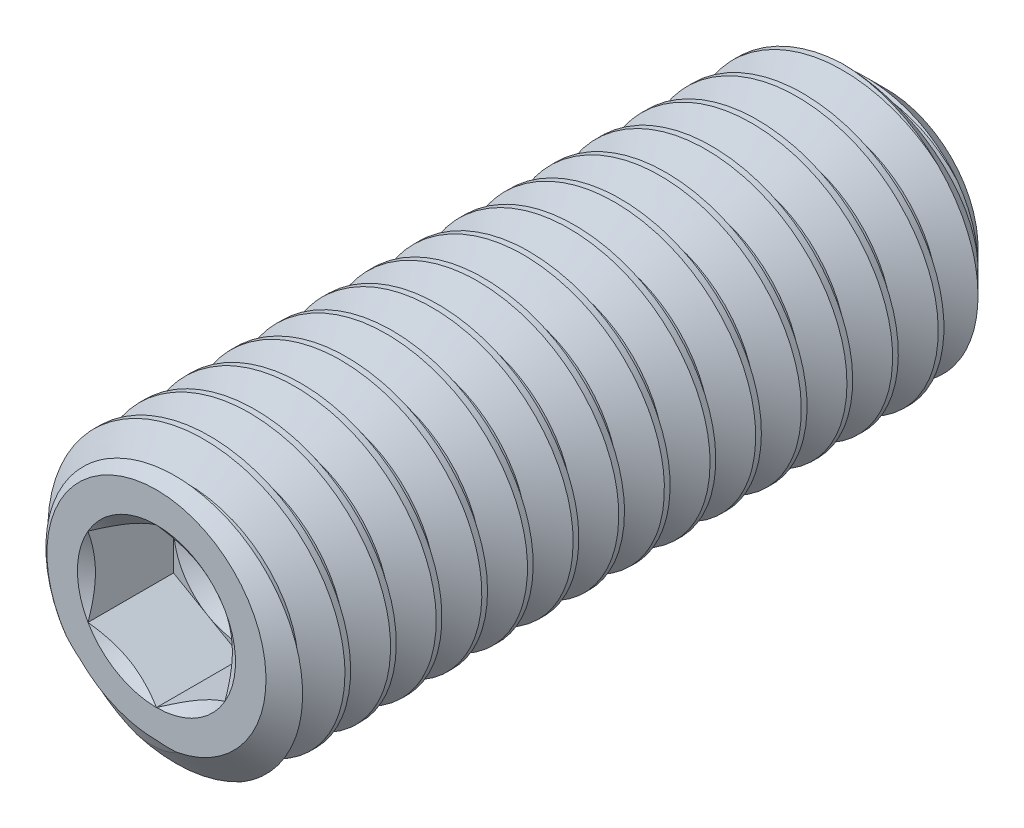
SolidWorks part; units mm, degrees
ref_plane "Front" through (0, 0, 0) normal (0, 0, 1) x (1, 0, 0)
ref_plane "Top" through (0, 0, 0) normal (0, 1, 0) x (1, 0, 0)
ref_plane "Right" through (0, 0, 0) normal (1, 0, 0) x (0, 0, -1)
sketch "Sketch22" plane through (0, 0, 0) normal (1, 0, 0) x (0, 0, -1)
  line L0 (-8, 0) -> (-8, 2.4)
  line L1 (-8, 2.4) -> (-7.5799, 3)
  line L2 (-7.5799, 3) -> (7, 3)
  line L3 (7, 3) -> (8, 2)
  line L4 (-0.2899, 3) -> (-0.2899, -3) construction
  line L5 (8, 0) -> (-8, 0)
  line L6 (-8, 2.4) -> (-8, -2.4) construction
  line L7 (8, 0) -> (8, 2)
  point P11 (-0.2899, 0)
  dimension "Length" = 16
  dimension "D3" = 35
  dimension "D6" = 45
  dimension "Dia" = 6
  dimension "D1" = 4.8
  dimension "D2" = 1
revolve "Revolve1" add sketch "Sketch22" angle 360 about L5
ref_plane "Plane1" through (0, 0, -8) normal (0, 0, 1) x (1, 0, 0)
sketch "Sketch27" plane through (0, 0, -8) normal (0, 0, 1) x (1, 0, 0)
  circle A0 centre (0, 0) radius 3 construction
  circle A1 centre (0, 0) radius 3
curve "Helix/Spiral1" pitch 1 height 17 radius 3 centre (0, 0, -8) axis (0, 0, 1) start towards (0, 1, 0)
sketch "Sketch28" plane through (0, 0, 0) normal (1, 0, 0) x (0, 0, -1)
  line L0 (8, 3) -> (8.875, 3)
  line L1 (8.875, 3) -> (8.5, 2.3505)
  line L2 (8.5, 2.3505) -> (8.375, 2.3505)
  line L3 (8.375, 2.3505) -> (8, 3)
  line L4 (8.1875, 2.6752) -> (8.6875, 2.6752) construction
  line L6 (-7.5799, 3) -> (7, 3) construction
  dimension "D1" = 0.125
  dimension "D3" = 60
  dimension "D2" = 0.5
sweep "Cut-Sweep2" cut profiles "Sketch28" path "Helix/Spiral1" align with end faces yes
sketch "Sketch23" plane through (0, 0, 8) normal (0, 0, 1) x (1, 0, 0)
  line L1 (0, 1.7321) -> (-1.5, 0.866)
  line L2 (-1.5, 0.866) -> (-1.5, -0.866)
  line L3 (-1.5, -0.866) -> (0, -1.7321)
  line L4 (0, -1.7321) -> (1.5, -0.866)
  line L5 (1.5, -0.866) -> (1.5, 0.866)
  line L6 (1.5, 0.866) -> (0, 1.7321)
  circle A0 centre (0, 0) radius 1.5 construction
  dimension "Hex" = 3
extrude "Cut-Extrude10" cut sketch "Sketch23" against normal blind 1.875
sketch "Sketch24" plane through (0, 0, 8) normal (0, 0, 1) x (1, 0, 0)
  circle A0 centre (0, 0) radius 1.7321
extrude "Cut-Extrude11" cut sketch "Sketch24" against normal through all draft 55
sketch "Sketch26" plane through (0, 0, 6.125) normal (0, 0, 1) x (1, 0, 0)
  circle A0 centre (0, 0) radius 1.5 construction
  circle A1 centre (0, 0) radius 1.5
extrude "Cut-Extrude12" cut sketch "Sketch26" against normal through all draft 60
sketch "Sketch30" plane through (0, 0, 0) normal (1, 0, 0) x (0, 0, -1)
  line L0 (-7.5799, 3) -> (7, 3) construction
  line L1 (-8, 0) -> (-8, 2.4) construction
  line L2 (8, 0) -> (8, 2) construction
  point P0 (-8, 3)
  point P1 (8, 3)
  point P2 (8, -3)
  point P11 (5.5, -3)
  dimension "D1" = 2.5
equation "\"D1@Sketch28\" = \"D4@Helix/Spiral1\" * .125"
equation "\"D2@Sketch28\" = \"D4@Helix/Spiral1\" * .5"
equation "\"D3@Helix/Spiral1\" = \"Length@Sketch22\" + \"D4@Helix/Spiral1\""
equation "\"D1@Sketch30\" = \"D4@Helix/Spiral1\" * 2.5"
equation "\"hex Depth@Cut-Extrude10\" = \"Hex@Sketch23\" * .625"
equation "\"D1@Sketch22\" = \"Dia@Sketch22\" * .8"
equation "\"D2@Sketch22\" = \"D4@Helix/Spiral1\""
